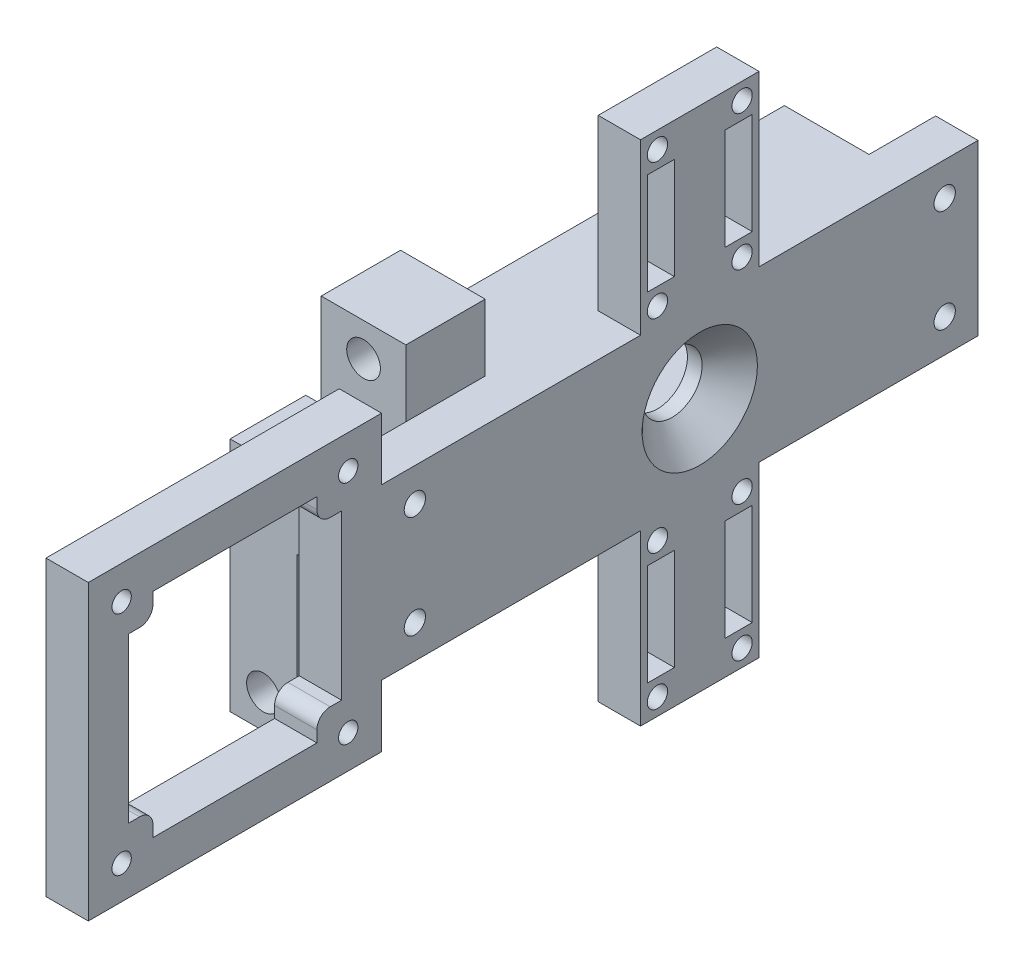
SolidWorks part; units mm, degrees
ref_plane "Front Plane" through (0, 0, 0) normal (0, 0, 1) x (1, 0, 0)
ref_plane "Top Plane" through (0, 0, 0) normal (0, 1, 0) x (1, 0, 0)
ref_plane "Right Plane" through (0, 0, 0) normal (1, 0, 0) x (0, 0, -1)
sketch "Sketch1" plane through (0, 0, 0) normal (0, 1, 0) x (1, 0, 0)
  line L1 (0, 0) -> (6.35, 0)
  line L2 (0, 0) -> (0, 89.5)
  line L3 (0, 89.5) -> (6.35, 89.5)
  line L4 (6.35, 0) -> (6.35, 89.5)
  dimension "D1" = 89.5
  dimension "D2" = 6.35
extrude "Boss-Extrude1" add sketch "Sketch1" along normal blind 25.4
sketch "Sketch2" plane through (0, 0, 0) normal (-1, 0, 0) x (0, 0, 1)
  line L0 (-89.5, 25.4) -> (0, 25.4) construction
  line L1 (-74.15, 20.05) -> (-21.35, 20.05)
  line L2 (-74.15, 20.05) -> (-74.15, 5.35)
  line L3 (-74.15, 5.35) -> (-21.35, 5.35)
  line L4 (-21.35, 20.05) -> (-21.35, 5.35)
  line L6 (-89.5, 25.4) -> (-89.5, 0) construction
  line L13 (-89.5, 0) -> (0, 0) construction
  line L14 (-79.5, 25.4) -> (-10, 25.4)
  line L15 (-79.5, 25.4) -> (-79.5, 0)
  line L16 (-79.5, 0) -> (-10, 0)
  line L17 (-10, 25.4) -> (-10, 0)
  line L18 (0, 25.4) -> (0, 0) construction
  dimension "D1" = 52.8
  dimension "D2" = 14.7
  dimension "D3" = 5.35
  dimension "D4" = 15.35
  dimension "D5" = 10
  dimension "D6" = 10
sketch "Sketch4" plane through (6.35, 0, 0) normal (1, 0, 0) x (0, 0, -1)
  line L0 (0, 25.4) -> (0, 0) construction
  line L1 (0, 34.7) -> (-44, 34.7)
  line L2 (0, 34.7) -> (0, -9.3)
  line L3 (0, -9.3) -> (-44, -9.3)
  line L4 (-44, 34.7) -> (-44, -9.3)
  line L6 (0, 25.4) -> (89.5, 25.4) construction
  circle A0 centre (-39, 29.7) radius 1.45
  circle A1 centre (-5, 29.7) radius 1.45
  circle A2 centre (-39, -4.3) radius 1.45
  circle A3 centre (-5, -4.3) radius 1.45
  dimension "D4" = 34
  dimension "D6" = 2.9
  dimension "D7" = 34
  dimension "D1" = 44
  dimension "D2" = 9.3
  dimension "D3" = 44
  dimension "D5" = 5
  dimension "D8" = 5
extrude "Boss-Extrude2" add sketch "Sketch4" against normal up to surface (6.35 mm away) up to face at (0, 12.7, -44.75)
hole_wizard "CSK for M8 Flat Head Machine Screw1" positions "Sketch6" profile "Sketch7" countersink size "M8" standard "ANSI Metric"
sketch "Sketch6" plane through (6.35, 0, 0) normal (1, 0, 0) x (0, 0, -1)
  line L1 (89.5, 25.4) -> (89.5, 0) construction
  line L2 (0, 25.4) -> (89.5, 25.4) construction
  point P0 (47.75, 12.7)
  dimension "D1" = 41.75
  dimension "D2" = 12.7
sketch "Sketch7" plane through (6.35, 12.7, -47.75) normal (0, 1, 0) x (0, 0, -1)
  line L0 (0, 0) -> (0, 20.2039)
  line L1 (0, 20.2039) -> (4.5, 17.5)
  line L2 (4.5, 17.5) -> (4.5, 4.15)
  line L3 (4.5, 4.15) -> (8.65, 0)
  line L5 (8.65, 0) -> (0, 0)
  line L6 (-4.5, 4.15) -> (-8.65, 0) construction
  line L10 (0, 20.2039) -> (-4.5, 17.5) construction
  line L11 (0, -6.35) -> (0, 107.95) construction
  dimension "Hole Dia." = 9
  dimension "Hole Depth" = 17.5
  dimension "Near C'Sink Dia." = 17.3
  dimension "Near C'Sink Angle" = 90
  dimension "Drill Angle" = 118
extrude "Boss-Extrude3" add sketch "Sketch2" along normal blind 12.7
sketch "Sketch9" plane through (0, 0, 0) normal (-1, 0, 0) x (0, 0, 1)
  line L1 (0, 34.7) -> (0, 25.4) construction
  line L2 (-10, 25.4) -> (0, 25.4) construction
  line L3 (-10, 0) -> (0, 0) construction
  line L4 (-89.5, 25.4) -> (-89.5, 0) construction
  circle A0 centre (-5, 20.4) radius 1.6
  circle A1 centre (-5, 5) radius 1.6
  circle A3 centre (-84.5, 5) radius 1.6
  circle A4 centre (-84.5, 20.4) radius 1.6
  dimension "D1" = 3.2
  dimension "D2" = 5
  dimension "D3" = 5
  dimension "D4" = 5
  dimension "D5" = 5
extrude "Cut-Extrude1" cut sketch "Sketch9" against normal up to surface (6.35 mm away) up to face at (6.35, 12.7, -56.4)
sketch "Sketch10" plane through (6.35, 0, 0) normal (1, 0, 0) x (0, 0, -1)
  line L0 (0, 25.4) -> (89.5, 25.4) construction
  line L1 (38.86, 25.4) -> (56.64, 25.4)
  line L2 (38.86, 25.4) -> (38.86, 50.8)
  line L3 (38.86, 50.8) -> (56.64, 50.8)
  line L4 (56.64, 25.4) -> (56.64, 50.8)
  line L5 (89.5, 25.4) -> (89.5, 0) construction
  line L7 (0, 0) -> (89.5, 0) construction
  line L8 (38.86, 0) -> (56.64, 0)
  line L9 (38.86, 0) -> (38.86, -25.4)
  line L10 (38.86, -25.4) -> (56.64, -25.4)
  line L11 (56.64, 0) -> (56.64, -25.4)
  circle A0 centre (41.4, 27.94) radius 1.524
  circle A1 centre (54.1, 27.94) radius 1.524
  circle A2 centre (54.1, 48.26) radius 1.524
  circle A3 centre (41.4, 48.26) radius 1.524
  circle A4 centre (41.4, -2.54) radius 1.524
  circle A5 centre (54.1, -2.54) radius 1.524
  circle A6 centre (41.4, -22.86) radius 1.524
  circle A7 centre (54.1, -22.86) radius 1.524
  point P25 (47.75, 50.8)
  dimension "D3" = 3.048
  dimension "D11" = 2.54
  dimension "D1" = 25.4
  dimension "D2" = 17.78
  dimension "D4" = 20.32
  dimension "D5" = 12.7
  dimension "D6" = 2.54
  dimension "D7" = 2.54
  dimension "D8" = 41.75
  dimension "D9" = 25.4
  dimension "D10" = 17.78
  dimension "D12" = 20.32
extrude "Boss-Extrude4" add sketch "Sketch10" against normal blind 6.35
sketch "Sketch11" plane through (6.35, 0, 0) normal (1, 0, 0) x (0, 0, -1)
  line L0 (0, 0) -> (38.86, 0) construction
  line L1 (39.876, -5.08) -> (43.94, -5.08)
  line L2 (39.876, -5.08) -> (39.876, -20.32)
  line L3 (39.876, -20.32) -> (43.94, -20.32)
  line L4 (43.94, -5.08) -> (43.94, -20.32)
  line L5 (51.56, -5.08) -> (55.624, -5.08)
  line L6 (51.56, -5.08) -> (51.56, -20.32)
  line L7 (51.56, -20.32) -> (55.624, -20.32)
  line L8 (55.624, -5.08) -> (55.624, -20.32)
  line L9 (38.86, -25.4) -> (56.64, -25.4) construction
  line L10 (38.86, 0) -> (38.86, -25.4) construction
  line L11 (56.64, -25.4) -> (56.64, 0) construction
  line L12 (56.64, 50.8) -> (38.86, 50.8) construction
  line L13 (39.876, 45.72) -> (43.94, 45.72)
  line L14 (39.876, 45.72) -> (39.876, 30.48)
  line L15 (39.876, 30.48) -> (43.94, 30.48)
  line L16 (43.94, 45.72) -> (43.94, 30.48)
  line L17 (51.56, 45.72) -> (55.624, 45.72)
  line L18 (51.56, 45.72) -> (51.56, 30.48)
  line L19 (51.56, 30.48) -> (55.624, 30.48)
  line L20 (55.624, 45.72) -> (55.624, 30.48)
  line L21 (0, 25.4) -> (38.86, 25.4) construction
  dimension "D1" = 5.08
  dimension "D2" = 5.08
  dimension "D3" = 1.016
  dimension "D4" = 4.064
  dimension "D5" = 1.016
  dimension "D6" = 5.08
  dimension "D7" = 5.08
extrude "Cut-Extrude2" cut sketch "Sketch11" against normal up to surface (6.35 mm away) up to face at (0, -22.86, -55.624)
sketch "Sketch14" plane through (0, 25.4, 0) normal (0, 1, 0) x (1, 0, 0)
  line L0 (-12.7, 10) -> (-12.7, 79.5) construction
  line L1 (0, 10) -> (-12.7, 10)
  line L2 (0, 10) -> (0, 21.9)
  line L3 (0, 21.9) -> (-12.7, 21.9)
  line L4 (-12.7, 10) -> (-12.7, 21.9)
  dimension "D1" = 11.9
extrude "Boss-Extrude5" add sketch "Sketch14" along normal blind 10
sketch "Sketch15" plane through (0, 0, -10) normal (0, 0, 1) x (1, 0, 0)
  line L0 (-12.7, 0) -> (-12.7, 35.4) construction
  line L1 (-12.7, 35.4) -> (0, 35.4) construction
  circle A0 centre (-6.35, 30.4) radius 2.5273
  dimension "D1" = 6.35
  dimension "D2" = 5.0546
  dimension "D3" = 5
extrude "Cut-Extrude4" cut sketch "Sketch15" against normal blind 7
sketch "Sketch16" plane through (-12.7, 0, 0) normal (-1, 0, 0) x (0, 0, 1)
  line L0 (-10, 0) -> (-10, 35.4) construction
  line L1 (-10, 10) -> (-21.35, 10)
  line L2 (-10, 10) -> (-10, 0)
  line L3 (-10, 0) -> (-21.35, 0)
  line L4 (-21.35, 10) -> (-21.35, 0)
  line L5 (-79.5, 0) -> (-10, 0) construction
  dimension "D1" = 10
  dimension "D2" = 11.35
extrude "Boss-Extrude6" add sketch "Sketch16" along normal blind 13.6718
sketch "Sketch17" plane through (0, 0, 0) normal (0, -1, 0) x (1, 0, 0)
  line L0 (-26.3718, -21.35) -> (-12.7, -21.35) construction
  line L1 (-26.3718, -10) -> (-16.3718, -10)
  line L2 (-26.3718, -10) -> (-26.3718, -21.35)
  line L3 (-26.3718, -21.35) -> (-16.3718, -21.35)
  line L4 (-16.3718, -10) -> (-16.3718, -21.35)
  dimension "D1" = 10
extrude "Boss-Extrude7" add sketch "Sketch17" along normal blind 25.4523
sketch "Sketch18" plane through (0, 0, -10) normal (0, 0, 1) x (1, 0, 0)
  line L0 (-16.3718, -25.4523) -> (-26.3718, -25.4523) construction
  line L1 (-26.3718, -25.4523) -> (-26.3718, 10) construction
  circle A0 centre (-21.3718, -20.4523) radius 2.5273
  circle A1 centre (-6.35, 30.4) radius 2.5273 construction
  dimension "D1" = 5
  dimension "D2" = 5
extrude "Cut-Extrude5" cut sketch "Sketch18" against normal blind 7
sketch "Sketch19" plane through (0, 0, 0) normal (0, -1, 0) x (1, 0, 0)
  line L0 (-12.7, -79.5) -> (-12.7, -21.35) construction
  line L1 (-12.7, -47.925) -> (-18.0384, -47.925)
  line L2 (-12.7, -47.925) -> (-12.7, -57.925)
  line L3 (-12.7, -57.925) -> (-18.0384, -57.925)
  line L4 (-18.0384, -47.925) -> (-18.0384, -57.925)
  line L5 (-16.3718, -21.35) -> (-12.7, -21.35) construction
  dimension "D1" = 10
  dimension "D2" = 26.575
  dimension "D3" = 5.3384
extrude "Boss-Extrude8" add sketch "Sketch19" against normal up to surface (5.35 mm away) up to face at (-6.35, 5.35, -47.75)
sketch "Sketch21" plane through (0, 0, 0) normal (0, -1, 0) x (1, 0, 0)
  line L5 (-16.9785, -26.9) -> (-8.8616, -26.9)
  line L6 (-16.9785, -26.9) -> (-16.9785, -31.9)
  line L7 (-16.9785, -31.9) -> (-8.8616, -31.9)
  line L8 (-8.8616, -26.9) -> (-8.8616, -31.9)
  line L10 (-16.9785, -64.9) -> (-8.8616, -64.9)
  line L11 (-16.9785, -64.9) -> (-16.9785, -69.9)
  line L12 (-16.9785, -69.9) -> (-8.8616, -69.9)
  line L13 (-8.8616, -64.9) -> (-8.8616, -69.9)
  line L17 (-16.3718, -21.35) -> (-12.7, -21.35) construction
  line L18 (-12.7, -47.925) -> (-12.7, -21.35) construction
  dimension "D3" = 5
  dimension "D4" = 43
  dimension "D5" = 5
  dimension "D7" = 8.1169
  dimension "D9" = 5.55
  dimension "D10" = 3.8384
extrude "Boss-Extrude9" add sketch "Sketch21" along normal blind 11.85
sketch "Sketch25" plane through (-18.0384, 0, 0) normal (-1, 0, 0) x (0, 0, 1)
  line L5 (-47.925, 5.35) -> (-47.925, 0) construction
  line L6 (-57.925, 5.35) -> (-47.925, 5.35)
  line L7 (-57.925, 5.35) -> (-57.925, 0)
  line L8 (-57.925, 0) -> (-47.925, 0)
  line L9 (-47.925, 5.35) -> (-47.925, 0)
  line L10 (-56.64, 0) -> (-38.86, 0) construction
extrude "Cut-Extrude7" cut sketch "Sketch25" against normal up to surface (5.3384 mm away) up to face at (-12.7, 13.7429, -47.4607)
sketch "Sketch26" plane through (6.35, 0, 0) normal (1, 0, 0) x (0, 0, -1)
  line L23 (-34.3, 28.7) -> (-9.7, 28.7)
  line L26 (-38, 25) -> (-38, 0.4)
  line L27 (-34.3, -3.3) -> (-9.7, -3.3)
  line L28 (-6, 25) -> (-6, 0.4)
  line L30 (-44, 34.7) -> (-44, -9.3) construction
  line L31 (-44, -9.3) -> (0, -9.3) construction
  line L33 (-34.3, 28.7) -> (-34.3, 25)
  line L34 (-38, 25) -> (-34.3, 25)
  line L35 (-9.7, 28.7) -> (-9.7, 25)
  line L36 (-9.7, 25) -> (-6, 25)
  line L37 (-6, 0.4) -> (-9.7, 0.4)
  line L38 (-9.7, 0.4) -> (-9.7, -3.3)
  line L39 (-38, 0.4) -> (-34.3, 0.4)
  line L40 (-34.3, 0.4) -> (-34.3, -3.3)
  line L41 (0, 25.4) -> (0, 34.7) construction
  line L42 (0, 34.7) -> (-44, 34.7) construction
  dimension "D5" = 3.7
  dimension "D6" = 3.7
  dimension "D9" = 3.7
  dimension "D11" = 3.7
  dimension "D7" = 6
  dimension "D2" = 3.7
  dimension "D3" = 6
  dimension "D4" = 6
  dimension "D8" = 3.7
  dimension "D10" = 3.7
  dimension "D12" = 6
extrude "Cut-Extrude8" cut sketch "Sketch26" against normal up to surface (6.35 mm away) up to face at (0, 5, -3.4)
fillet "Fillet1" radius 2 4 edges at (3.175, 25, 9.7) (3.175, 0.4, 34.3) (3.175, 0.4, 9.7) (3.175, 25, 34.3)
equation "\"D1@Cut-Extrude4\"=4"
